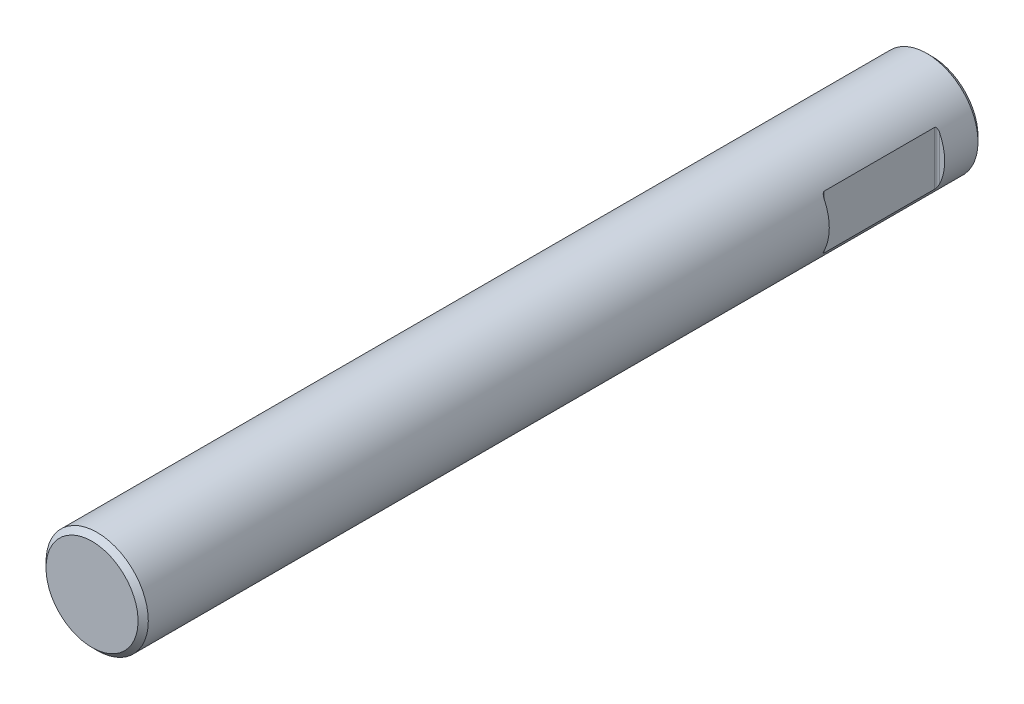
SolidWorks part; units mm, degrees
material "1.4000 (X6Cr13)"
ref_plane "Ebene vorne" through (0, 0, 0) normal (0, 0, 1) x (1, 0, 0)
ref_plane "Ebene oben" through (0, 0, 0) normal (0, 1, 0) x (1, 0, 0)
ref_plane "Ebene rechts" through (0, 0, 0) normal (1, 0, 0) x (0, 0, -1)
sketch "Skizze1" plane through (0, 0, 0) normal (1, 0, 0) x (0, 0, -1)
  line L0 (-50.5169, 0) -> (54.2703, 0) construction
  line L1 (0, 19.5371) -> (0, -16.0786) construction
  line L2 (0, 0) -> (0, 1.995)
  line L4 (32.76, 1.995) -> (32.76, 0)
  line L5 (32.76, 0) -> (0, 0)
  line L9 (0, 1.995) -> (32.76, 1.995)
  dimension "D1" = 3.99
  dimension "D2" = 32.76
revolve "Rotation1" add sketch "Skizze1" angle 360 about L0
ref_axis "Achse1" through (0, 0, 54.9615) along (0, 0, -1)
chamfer "Fase1" distance 0.2 angle 45 2 edges at (1.995, 0, -32.76) (1.995, 0, 0)
sketch "Skizze2" plane through (0, 0, 0) normal (0, 1, 0) x (1, 0, 0)
  line L0 (1.795, 32.76) -> (-1.795, 32.76) construction
  line L7 (-6.2, 26.76) -> (-1.8, 26.76)
  line L8 (-6.2, 26.76) -> (-6.2, 31.26)
  line L9 (-6.2, 31.26) -> (-1.8, 31.26)
  line L10 (-1.7, 26.86) -> (-1.7, 31.16)
  line L11 (-6.2, 26.76) -> (-1.7, 31.26) construction
  line L12 (-6.2, 31.26) -> (-1.7, 26.76) construction
  line L13 (0, -7.285) -> (0, 53.978) construction
  line L14 (-1.995, 40.456) -> (-1.995, -1.4737) construction
  line L15 (-1.995, 32.56) -> (-1.995, 0.2) construction
  line L16 (6.2, 31.26) -> (1.7, 26.76) construction
  line L17 (6.2, 26.76) -> (1.7, 31.26) construction
  line L20 (1.7, 26.86) -> (1.7, 31.16)
  line L21 (6.2, 31.26) -> (1.8, 31.26)
  line L22 (6.2, 26.76) -> (6.2, 31.26)
  line L23 (6.2, 26.76) -> (1.8, 26.76)
  arc A0 (1.7, 31.16) -> (1.8, 31.26) centre (1.8, 31.16) cw
  arc A1 (1.8, 26.76) -> (1.7, 26.86) centre (1.8, 26.86) cw
  arc A6 (-1.8, 26.76) -> (-1.7, 26.86) centre (-1.8, 26.86) ccw
  arc A7 (-1.7, 31.16) -> (-1.8, 31.26) centre (-1.8, 31.16) ccw
  point P5 (-3.95, 29.01)
  point P19 (-1.7293, 31.2307)
  point P20 (-1.7293, 26.7893)
  point P57 (1.7293, 26.7893)
  point P58 (1.7293, 31.2307)
  point P59 (3.95, 29.01)
  dimension "D2" = 0.1
  dimension "D1" = 3.4
  dimension "D3" = 4.5
  dimension "D4" = 1.5
  dimension "D7" = 4.3
extrude "Schnitt-Linear austragen1" cut sketch "Skizze2" against normal through all and the other way through all
